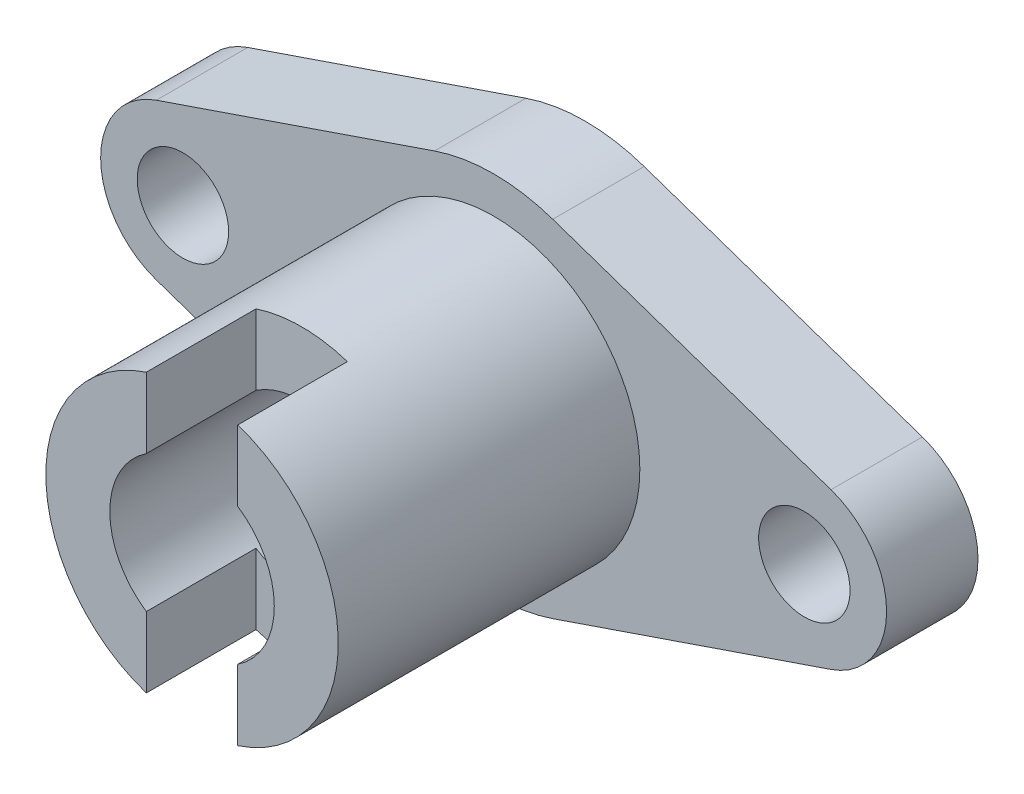
SolidWorks part; units mm, degrees
ref_plane "前视基准面" through (0, 0, 0) normal (0, 0, 1) x (1, 0, 0)
ref_plane "上视基准面" through (0, 0, 0) normal (0, 1, 0) x (1, 0, 0)
ref_plane "右视基准面" through (0, 0, 0) normal (1, 0, 0) x (0, 0, -1)
other "Configuration Table"
sketch "草图1" plane through (0, 0, 0) normal (0, 0, 1) x (1, 0, 0)
  line L0 (-36.9118, 8.516) -> (-6.4706, 18.9244)
  line L1 (-36.9118, -8.516) -> (-6.4706, -18.9244)
  line L3 (36.9118, -8.516) -> (6.4706, -18.9244)
  line L4 (36.9118, 8.516) -> (6.4706, 18.9244)
  arc A6 (-6.4706, -18.9244) -> (6.4706, -18.9244) centre (0, 0) ccw
  arc A7 (-36.9118, 8.516) -> (-36.9118, -8.516) centre (-34, 0) ccw
  circle A8 centre (-34, 0) radius 5
  circle A9 centre (34, 0) radius 5
  arc A10 (36.9118, 8.516) -> (36.9118, -8.516) centre (34, 0) cw
  arc A11 (6.4706, 18.9244) -> (-6.4706, 18.9244) centre (0, 0) ccw
  dimension "D1" = 34
extrude "凸台-拉伸1" add sketch "草图1" along normal blind 10 contours L0 A11 L4 A10 L3 A6 L1 A7
sketch "草图3" plane through (0, 0, 0) normal (0, 0, 1) x (1, 0, 0)
  circle A0 centre (-34, 0) radius 5
  circle A1 centre (34, 0) radius 5
extrude "切除-拉伸1" cut sketch "草图3" along normal blind 10
sketch "草图4" plane through (0, 0, 10) normal (0, 0, 1) x (1, 0, 0)
  circle A0 centre (0, 0) radius 16
extrude "凸台-拉伸2" add sketch "草图4" along normal blind 33
sketch "草图5" plane through (0, 0, 43) normal (0, 0, 1) x (1, 0, 0)
  circle A0 centre (0, 0) radius 9
extrude "切除-拉伸2" cut sketch "草图5" against normal blind 89
sketch "草图6" plane through (0, 0, 0) normal (0, 1, 0) x (1, 0, 0)
  line L0 (-16, -43) -> (16, -43) construction
  line L1 (5, -43) -> (-5, -43)
  line L2 (5, -43) -> (5, -31)
  line L3 (5, -31) -> (-5, -31)
  line L4 (-5, -43) -> (-5, -31)
  line L5 (5, -43) -> (-5, -31) construction
  line L6 (5, -31) -> (-5, -43) construction
  point P0 (0, -34.8668)
  point P5 (0, 0)
  point P6 (0, 0)
  point P7 (0, 0)
  point P8 (0, 0)
  dimension "D1" = 10
  dimension "D2" = 12
extrude "切除-拉伸3" cut sketch "草图6" against normal blind 89 and the other way blind 89
